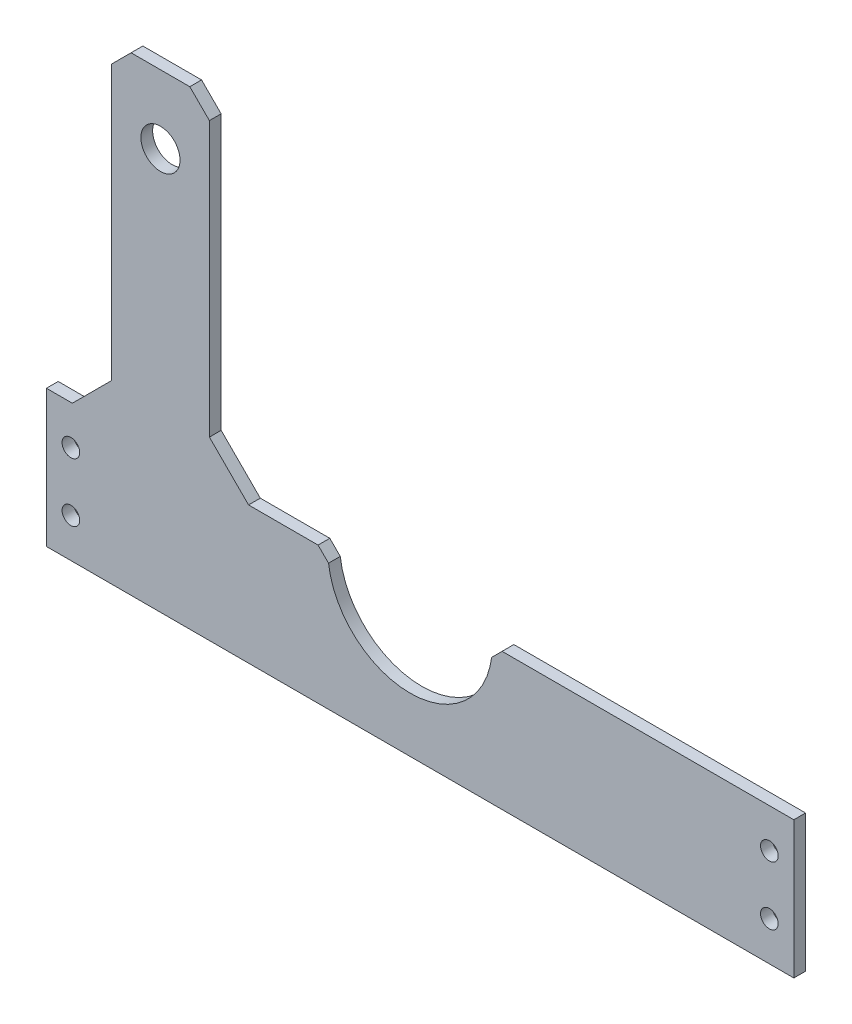
SolidWorks part; units mm, degrees
ref_plane "Front Plane" through (0, 0, 0) normal (0, 0, 1) x (1, 0, 0)
ref_plane "Top Plane" through (0, 0, 0) normal (0, 1, 0) x (1, 0, 0)
ref_plane "Right Plane" through (0, 0, 0) normal (1, 0, 0) x (0, 0, -1)
sketch "Sketch1" plane through (0, 0, 0) normal (0, 0, 1) x (1, 0, 0)
  line L0 (0, 17.5) -> (0, -17.5) construction
  line L1 (-95.435, -17.5) -> (95.435, -17.5)
  line L2 (-95.435, -17.5) -> (-95.435, 17.5)
  line L3 (-95.435, 17.5) -> (95.435, 17.5)
  line L4 (95.435, -17.5) -> (95.435, 17.5)
  point P6 (0, 0)
  dimension "D1" = 190.87
  dimension "D2" = 35
extrude "Boss-Extrude1" add sketch "Sketch1" along normal mid plane 3
sketch "Sketch2" plane through (0, 0, 1.5) normal (0, 0, 1) x (1, 0, 0)
  line L1 (95.435, -17.5) -> (95.435, 17.5) construction
  line L3 (95.435, 17.5) -> (-95.435, 17.5) construction
  circle A0 centre (-2.565, 17.5) radius 21
  dimension "D1" = 42
  dimension "D2" = 98
extrude "Cut-Extrude1" cut sketch "Sketch2" against normal through all
sketch "Sketch3" plane through (0, 17.5, 0) normal (0, 1, 0) x (1, 0, 0)
  line L0 (95.435, 1.5) -> (18.435, 1.5) construction
  line L1 (-53.815, -1.5) -> (-78.815, -1.5)
  line L2 (-53.815, -1.5) -> (-53.815, 1.5)
  line L3 (-53.815, 1.5) -> (-78.815, 1.5)
  line L4 (-78.815, -1.5) -> (-78.815, 1.5)
  line L5 (-23.565, -1.5) -> (-95.435, -1.5) construction
  line L6 (-95.435, -1.5) -> (-95.435, 1.5) construction
  dimension "D1" = 25
  dimension "D2" = 16.62
extrude "Boss-Extrude2" add sketch "Sketch3" along normal blind 85
sketch "Sketch4" plane through (0, 0, 1.5) normal (0, 0, 1) x (1, 0, 0)
  line L0 (-66.315, 102.5) -> (-66.315, 85) construction
  line L1 (-78.815, 102.5) -> (-53.815, 102.5) construction
  circle A0 centre (-66.315, 85) radius 5
  dimension "D2" = 10
  dimension "D1" = 17.5
chamfer "Chamfer1" distance 5 angle 45 2 edges at (-78.815, 102.5, 0) (-53.815, 102.5, 0)
extrude "Cut-Extrude2" cut sketch "Sketch4" against normal up to next contours A0
chamfer "Chamfer2" distance 10 angle 45 2 edges at (-53.815, 17.5, 0) (-78.815, 17.5, 0)
hole_wizard "M4 Clearance Hole1" positions "Sketch5" profile "Sketch6" hole size "M4" standard "ANSI Metric" end condition through all
sketch "Sketch5" plane through (0, 0, -1.5) normal (0, 0, -1) x (-1, 0, 0)
  point P0 (-89.185, 7.5)
  point P2 (-89.185, -7.5)
  point P9 (89.19, 7.5)
  point P11 (89.19, -7.5)
sketch "Sketch6" plane through (89.185, 7.5, -1.5) normal (1, 0, 0) x (0, 1, 0)
  line L0 (0, 0) -> (0, 3)
  line L1 (0, 3) -> (2.25, 3)
  line L2 (2.25, 3) -> (2.25, 0)
  line L5 (2.25, 0) -> (0, 0)
  line L11 (0, -6.35) -> (0, 107.95) construction
  dimension "Thru Hole Dia." = 4.5
  dimension "Thru Hole Depth" = 3
chamfer "Chamfer3" distance 2.5 angle 45 2 edges at (-23.565, 17.5, 0) (18.435, 17.5, 0)
